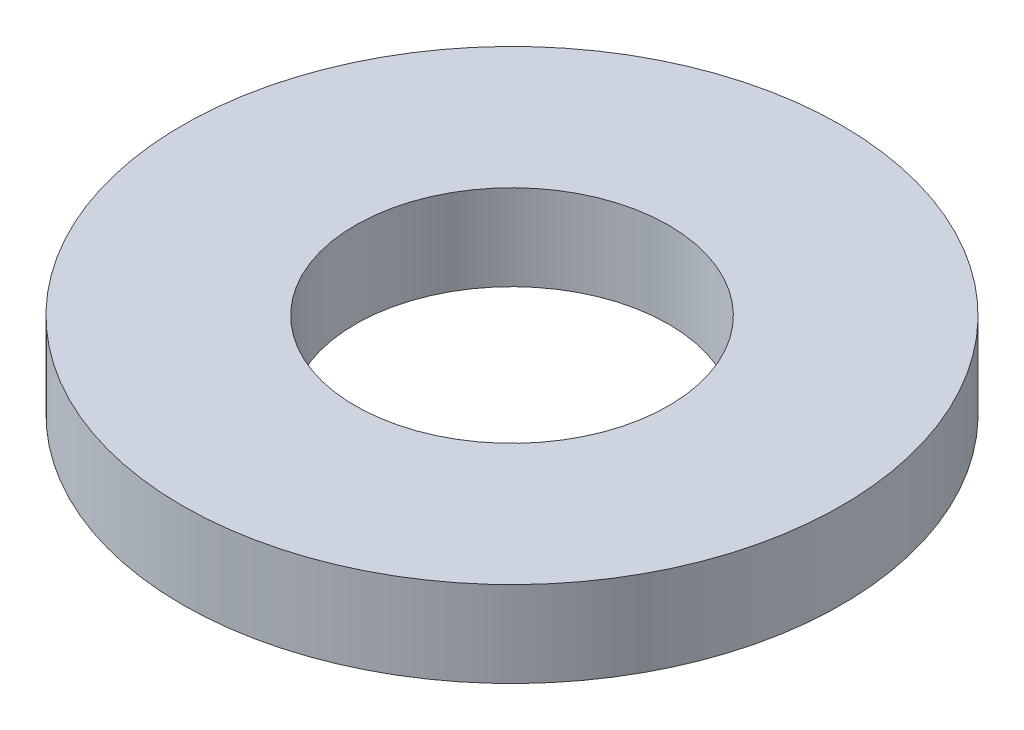
SolidWorks part; units mm, degrees
ref_plane "Front Plane" through (0, 0, 0) normal (0, 0, 1) x (1, 0, 0)
ref_plane "Top Plane" through (0, 0, 0) normal (0, 1, 0) x (1, 0, 0)
ref_plane "Right Plane" through (0, 0, 0) normal (1, 0, 0) x (0, 0, -1)
sketch "Sketch1" plane through (0, 0, 0) normal (0, 1, 0) x (1, 0, 0)
  circle A0 centre (0, 0) radius 100
  dimension "FLANGE_OD" = 200
extrude "Boss-Extrude1" add sketch "Sketch1" along normal blind 26
sketch "Sketch2" plane through (0, 0, 0) normal (0, 1, 0) x (1, 0, 0)
  circle A0 centre (0, 0) radius 47.5
  dimension "BORE_D" = 95
extrude "Cut-Extrude1" cut sketch "Sketch2" along normal through all
sketch "Sketch3" plane through (0, 26, 0) normal (0, 1, 0) x (1, 0, 0)
  circle A0 centre (0, 0) radius 39.7587 construction
  circle A1 centre (-39.7587, 0) radius 2.5119
  dimension "BOLT_D" = 5.0238
  dimension "BOLT_PCD" = 79.5174
extrude "Cut-Extrude2" cut sketch "Sketch3" against normal blind 23.5651 rebuild error yes
pattern_circular "CirPattern1" count 6 over 360 rebuild error yes
